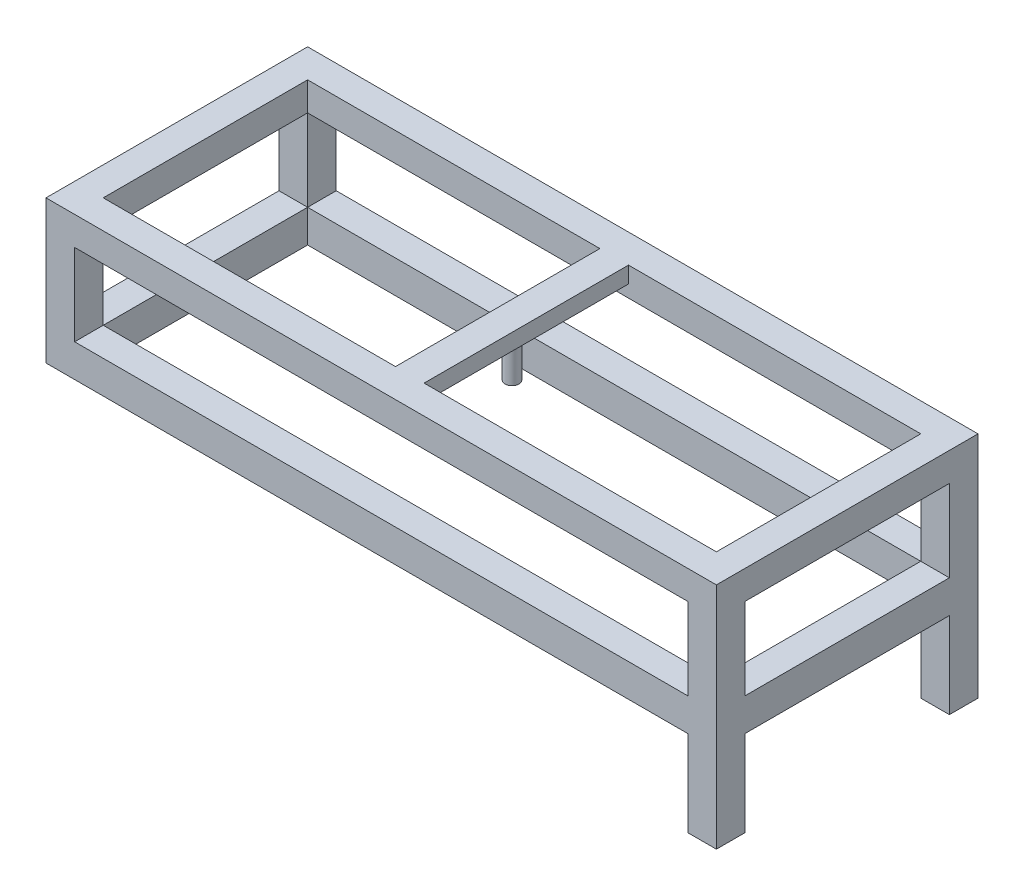
SolidWorks part; units mm, degrees
ref_plane "Front Plane" through (0, 0, 0) normal (0, 0, 1) x (1, 0, 0)
ref_plane "Top Plane" through (0, 0, 0) normal (0, 1, 0) x (1, 0, 0)
ref_plane "Right Plane" through (0, 0, 0) normal (1, 0, 0) x (0, 0, -1)
sketch "Sketch2" plane through (0, 0, 0) normal (0, 1, 0) x (1, 0, 0)
  line L0 (35, 285) -> (35, 35)
  line L1 (0, 320) -> (820, 320)
  line L2 (0, 320) -> (0, 0)
  line L3 (0, 0) -> (820, 0)
  line L4 (820, 320) -> (820, 0)
  line L5 (35, 35) -> (785, 35)
  line L6 (785, 285) -> (785, 35)
  line L7 (35, 285) -> (785, 285)
  line L8 (392.5, 35) -> (392.5, 285)
  line L9 (427.5, 35) -> (427.5, 285)
  line L10 (410, 285) -> (410, 35) construction
  dimension "D2" = 35
  dimension "D3" = 820
  dimension "D4" = 320
  dimension "D1" = 35
extrude "Boss-Extrude1" add sketch "Sketch2" against normal blind 35 contours L4 L1 L2 L3 L0 L7 L6 L5 region at (410, 0, -311.1977)
sketch "Sketch7" plane through (0, 0, 0) normal (0, 1, 0) x (1, 0, 0)
  line L0 (35, 35) -> (785, 35) construction
  line L1 (35, 285) -> (785, 285) construction
  line L2 (392.5, 285) -> (427.5, 285)
  line L3 (392.5, 285) -> (392.5, 35)
  line L4 (392.5, 35) -> (427.5, 35)
  line L5 (427.5, 285) -> (427.5, 35)
  point P8 (410, 35)
  dimension "D1" = 35
extrude "Boss-Extrude6" add sketch "Sketch7" against normal blind 20
sketch "Sketch3" plane through (0, -35, 0) normal (0, -1, 0) x (-1, 0, 0)
  line L1 (0, 0) -> (-35, 0)
  line L2 (0, 0) -> (0, 35)
  line L3 (0, 35) -> (-35, 35)
  line L4 (-35, 0) -> (-35, 35)
  line L5 (0, 320) -> (-35, 320)
  line L6 (0, 320) -> (0, 285)
  line L7 (0, 285) -> (-35, 285)
  line L8 (-35, 320) -> (-35, 285)
  line L9 (-785, 285) -> (-820, 285)
  line L10 (-785, 285) -> (-785, 320)
  line L11 (-785, 320) -> (-820, 320)
  line L12 (-820, 285) -> (-820, 320)
  line L13 (-785, 35) -> (-820, 35)
  line L14 (-785, 35) -> (-785, 0)
  line L15 (-785, 0) -> (-820, 0)
  line L16 (-820, 35) -> (-820, 0)
extrude "Boss-Extrude2" add sketch "Sketch3" along normal blind 100
sketch "Sketch4" plane through (0, -135, 0) normal (0, -1, 0) x (1, 0, 0)
  line L1 (0, 0) -> (820, 0)
  line L2 (0, 0) -> (0, -320)
  line L3 (0, -320) -> (820, -320)
  line L4 (820, 0) -> (820, -320)
  line L5 (785, -285) -> (35, -285)
  line L6 (785, -285) -> (785, -35)
  line L7 (785, -35) -> (35, -35)
  line L8 (35, -285) -> (35, -35)
extrude "Boss-Extrude3" add sketch "Sketch4" along normal blind 40
sketch "Sketch5" plane through (0, -175, 0) normal (0, -1, 0) x (1, 0, 0)
  line L1 (820, 0) -> (785, 0)
  line L2 (820, 0) -> (820, -35)
  line L3 (820, -35) -> (785, -35)
  line L4 (785, 0) -> (785, -35)
  line L5 (785, -285) -> (820, -285)
  line L6 (785, -285) -> (785, -320)
  line L7 (785, -320) -> (820, -320)
  line L8 (820, -285) -> (820, -320)
extrude "Boss-Extrude4" add sketch "Sketch5" along normal blind 105
shell "Shell1" thickness 1.5 removed face at (802.5, -280, -302.5) removed face at (802.5, -280, -17.5)
sketch "Sketch6" plane through (0, 0, 0) normal (0, -1, 0) x (-1, 0, 0)
  circle A0 centre (-410, 160) radius 8.5
  dimension "D1" = 17
  dimension "D2" = 410
  dimension "D3" = 160
extrude "Boss-Extrude5" add sketch "Sketch6" along normal blind 48 from offset 20
sketch "Sketch8" plane through (0, -68, 0) normal (0, -1, 0) x (1, 0, 0)
  circle A0 centre (410, -160) radius 4
  circle A1 centre (410, -160) radius 8.5 construction
  dimension "D1" = 8
extrude "Cut-Extrude1" cut sketch "Sketch8" against normal blind 30
equation "\"L_base\" = 820"
equation "\"D3@Sketch2\"=\"L_base\""
equation "\"larg_base\" = 320"
equation "\"D4@Sketch2\"=\"larg_base\""
equation "\"d_ext_rouleau\"= 90"
equation "\"epaisseur_rouleau\"=80"
equation "\"alesage-rouleau\"= 52"
equation "\"jeu_dent_rouleau\"= 2"
equation "\"profondeur_dent_rouleau\"=4"
equation "\"n_dent_roueau\"= 15"
equation "\"d_ext_roulement_rouleau\"= 42"
equation "\"d_int_roulement_rouleau\"= 20"
equation "\"B_roulement_rouleau\"= 12"
equation "\"r_roulement_rouleau\"= 0.6"
equation "\"d_bille_roulement_rouleau\"= 8"
equation "\"F_anneau_alesage_rouleau\"=1.85"
equation "\"G_anneau_alesage_rouleau\"=47.5"
equation "\"K_anneau_alesage_rouleau\"=3.75"
equation "\"d_vis_flasque_rouleau\"=5"
equation "\"l-x_vis_flasque_rouleau\"=4"
equation "\"g_anneau_arbre_rouleau\"=19"
equation "\"f_anneau_arbre_rouleau\"=1.3"
equation "\"k_anneau_arbre_rouleau\"=1.5"
equation "\"entrax_vis_rouleau\"=65"
equation "\"d_granulat\"= 8"
equation "\"h_matrice\"= 22"
equation "\"d_matrice\"= 220"
equation "\"zone_vide_matrice\" = 48"
equation "\"d_alesage_matrice\"=20"
equation "\"a_clavette_alesage_matrice\"=6"
equation "\"h_epaulement_arbre_matrice\" = 80"
equation "\"j_clavette_arbre_matrice\" = 6"
equation "\"g_anneaux_arbre_matrice\" = 19"
equation "\"f_anneaux_arbre_matrice\" = 1.3"
equation "\"e_anneaux_arbre_matrice\" = 1.2"
equation "\"B_roulement_bc_arbre_matrice\"= 10"
equation "\"h_polie_matrice\" = 40"
equation "\"l_arbre_matrice\" = 300"
equation "\"d_int_ecrou_encouch_matrice\" = 20"
equation "\"d_ext_ecrou_encouch_matrice\" = 32"
equation "\"b_ecrou_encouch_matrice\" = 6"
equation "\"s_ecrou_encouch_matrice\" = 4"
equation "\"G_ecrou_encouch_matrice\" = 1"
equation "\"E_ecrou_encouch_matrice\" = 4"
equation "\"d_int_roulement_conique_matrice\"=25"
equation "\"d_ext_roulement_conique_matrice\"=52"
equation "\"b_roulement_conique_matrice\"=16.25"
equation "\"d_int_roulement_bc_matrice\"=20"
equation "\"d_ext_roulement_bc_matrice\"=42"
equation "\"b_roulement_bc_matrice\" = 12"
equation "\"d_tube_sup_carter\"=244.5"
equation "\"e_tube_sup_carter\"=12"
equation "\"d_tube_inf_catrer\"= 168.3"
equation "\"e_tube_inf_carter\"= 6"
equation "\"d_tube_inf_carter_cache\" = 244.5"
equation "\"e_tube_inf_carter_cache\" = 8"
equation "\"d_tube_sup_carter_cache\" = 133"
equation "\"e_tube_sup_carter_cache\" = 4"
equation "\"h_tube_trimee\" = 40"
equation "\"e_tole\" = 8"
equation "\"entraxe_vis_carter\" = 196"
equation "\"d_int_polie_matrice\" = 16"
equation "\"D2@Sketch6\"=\"L_base\"/2"
equation "\"D3@Sketch6\"=\"larg_base\"/2"
